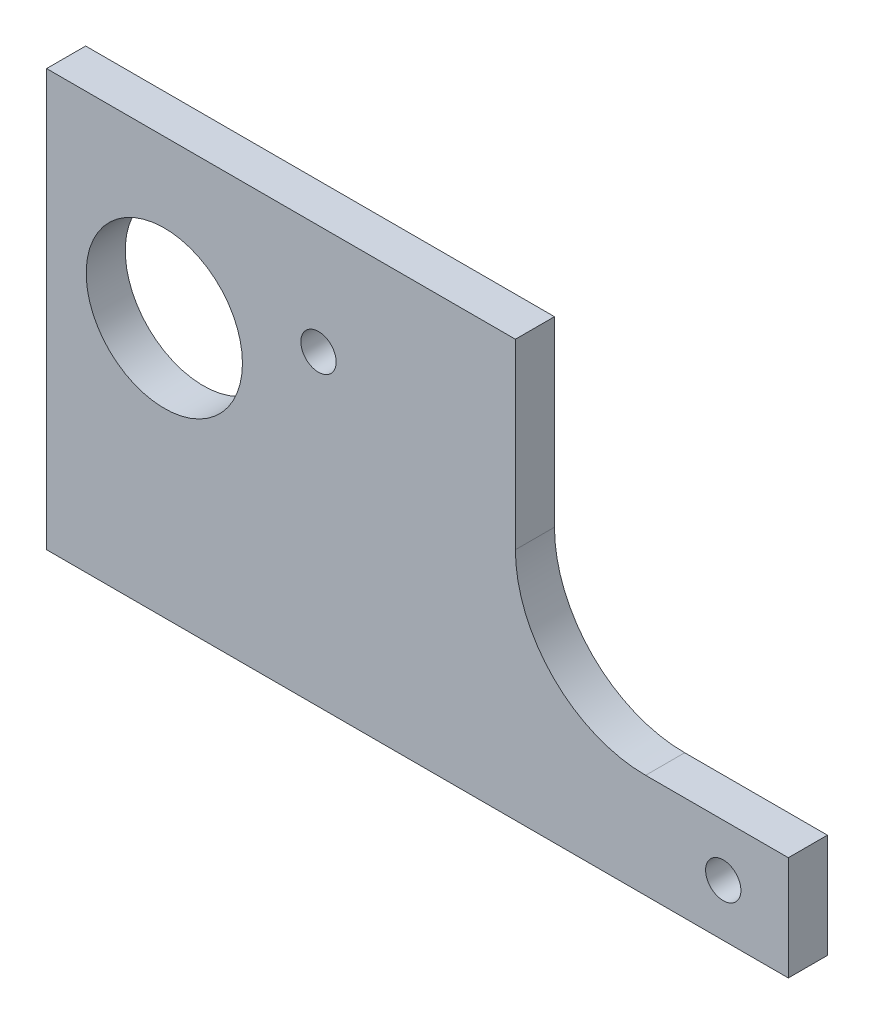
SolidWorks part; units mm, degrees
material "Acrylic (Medium-high impact)"
ref_plane "Front Plane" through (0, 0, 0) normal (0, 0, 1) x (1, 0, 0)
ref_plane "Top Plane" through (0, 0, 0) normal (0, 1, 0) x (1, 0, 0)
ref_plane "Right Plane" through (0, 0, 0) normal (1, 0, 0) x (0, 0, -1)
sketch "Sketch1" plane through (0, 0, 0) normal (0, 0, 1) x (1, 0, 0)
  line L6 (93.599, -41.275) -> (76.2, -41.275)
  line L7 (60.325, -25.4) -> (60.325, -3.175)
  line L8 (60.325, -3.175) -> (3.175, -3.175)
  line L9 (3.175, -3.175) -> (3.175, -53.975)
  line L10 (3.175, -53.975) -> (93.599, -53.975)
  line L11 (93.599, -53.975) -> (93.599, -41.275)
  line L12 (93.599, -41.275) -> (76.2, -41.275)
  line L13 (60.325, -25.4) -> (60.325, -3.175)
  line L14 (60.325, -3.175) -> (3.175, -3.175)
  line L15 (3.175, -3.175) -> (3.175, -53.975)
  line L16 (3.175, -53.975) -> (93.599, -53.975)
  line L17 (93.599, -53.975) -> (93.599, -41.275)
  arc A1 (60.325, -25.4) -> (76.2, -41.275) centre (76.2, -25.4) ccw
  arc A2 (60.325, -25.4) -> (76.2, -41.275) centre (76.2, -25.4) ccw
  dimension "D1" = 0
extrude "Boss-Extrude1" add sketch "Sketch1" along normal blind 4.7625
hole_wizard "3/4 (0.75) Diameter Hole1" positions "Sketch3" profile "Sketch2" hole size "3/4" standard "ANSI Inch" end condition through all
sketch "Sketch3" plane through (0, 0, 4.7625) normal (0, 0, 1) x (1, 0, 0)
  point P0 (17.526, -22.352)
sketch "Sketch2" plane through (17.526, -22.352, 4.7625) normal (1, 0, 0) x (0, -1, 0)
  line L0 (0, 0) -> (0, 4.7625)
  line L1 (0, 4.7625) -> (9.525, 4.7625)
  line L2 (9.525, 4.7625) -> (9.525, 0)
  line L5 (9.525, 0) -> (0, 0)
  line L11 (0, -6.35) -> (0, 107.95) construction
  dimension "Thru Hole Dia." = 19.05
  dimension "Thru Hole Depth" = 4.7625
hole_wizard "#6 Clearance Hole1" positions "Sketch5" profile "Sketch4" hole size "#6" standard "ANSI Inch" end condition through all
sketch "Sketch5" plane through (0, 0, 4.7625) normal (0, 0, 1) x (1, 0, 0)
  point P0 (36.322, -16.51)
  point P3 (85.6615, -47.625)
sketch "Sketch4" plane through (36.322, -16.51, 4.7625) normal (1, 0, 0) x (0, -1, 0)
  line L0 (0, 0) -> (0, 4.7625)
  line L1 (0, 4.7625) -> (2.1526, 4.7625)
  line L2 (2.1526, 4.7625) -> (2.1526, 0)
  line L5 (2.1526, 0) -> (0, 0)
  line L11 (0, -6.35) -> (0, 107.95) construction
  dimension "Thru Hole Dia." = 4.3053
  dimension "Thru Hole Depth" = 4.7625
